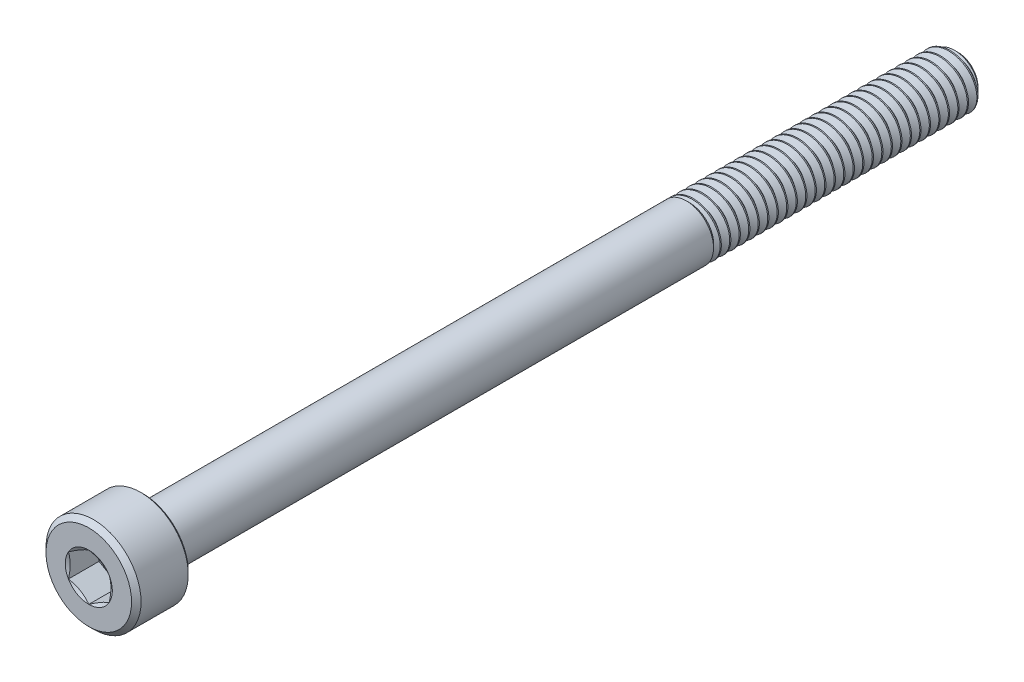
SolidWorks part; units mm, degrees
ref_plane "Front Plane" through (0, 0, 0) normal (0, 0, 1) x (1, 0, 0)
ref_plane "Top Plane" through (0, 0, 0) normal (0, 1, 0) x (1, 0, 0)
ref_plane "Right Plane" through (0, 0, 0) normal (1, 0, 0) x (0, 0, -1)
sketch "Sketch1" plane through (0, 0, 0) normal (1, 0, 0) x (0, 0, -1)
  line L0 (32, 0) -> (-32, 0) construction
  line L1 (-32, 0) -> (-32, 3.5) construction
  line L2 (-28, 2) -> (-28, 0) construction
  line L3 (31.3, 0) -> (31.3, 0.7) construction
  line L4 (12, 0) -> (12, -2) construction
  line L5 (12, 2) -> (32, 2) construction
  line L6 (32, -2) -> (32, 2) construction
  point P6 (-32, -1.5)
  point P9 (-32, 1.5)
  point P10 (12, 0)
  point P15 (-25.375, 0)
  point P16 (-23.4062, 0)
  point P17 (9.375, 0)
  point P18 (29.55, -2)
  point P22 (32, 0)
  dimension "Head Diameter" = 7
  dimension "Head Height" = 4
  dimension "Thread Size" = 4
  dimension "Length" = 60
  dimension "Thread Pitch" = 0.7
  dimension "Drive Size" = 3
  dimension "D1" = 0.7
  dimension "Min Thread Length" = 20
  dimension "D2" = 2.45
  dimension "D3" = 2.625
  dimension "D4" = 2.625
  dimension "D5" = 1.9688
sketch "Sketch2" plane through (0, 0, 0) normal (1, 0, 0) x (0, 0, -1)
  line L0 (32, 1.475) -> (31.475, 2)
  line L1 (-32, 3.5) -> (-28, 3.5)
  line L2 (-32, 3.5) -> (-32, 0)
  line L4 (-28, 3.5) -> (-28, 2)
  line L5 (-28, 2) -> (31.475, 2)
  line L8 (32, 1.475) -> (32, 0)
  line L9 (32, 0) -> (-32, 0) construction
  line L10 (32, 0) -> (-32, 0)
  dimension "D1" = 135
  dimension "D2" = 0.525
revolve "Revolve1" add sketch "Sketch2" angle 360 about L10
sketch "Sketch4" plane through (0, 0, 32) normal (0, 0, 1) x (1, 0, 0)
  line L1 (0, 1.7321) -> (-1.5, 0.866)
  line L2 (-1.5, 0.866) -> (-1.5, -0.866)
  line L3 (-1.5, -0.866) -> (0, -1.7321)
  line L4 (0, -1.7321) -> (1.5, -0.866)
  line L5 (1.5, -0.866) -> (1.5, 0.866)
  line L6 (1.5, 0.866) -> (0, 1.7321)
  circle A0 centre (0, 0) radius 1.5 construction
  circle A1 centre (0, 0) radius 3.5 construction
  circle A2 centre (0, 0) radius 3.5 construction
  circle A4 centre (0, 0) radius 3.5
  circle A5 centre (0, 0) radius 3.5 construction
  dimension "D1" = 3
extrude "Cut-Extrude1" cut sketch "Sketch4" against normal blind 2.25
sketch "Sketch5" plane through (0, 0, 32) normal (0, 0, 1) x (1, 0, 0)
  circle A0 centre (0, 0) radius 1.7321
extrude "Cut-Extrude2" cut sketch "Sketch5" against normal blind 10 draft 60
chamfer "Chamfer1" distance 0.35 angle 45 1 edges at (-3.5, 0, 32)
chamfer "Chamfer2" distance 0.175 angle 45 1 edges at (-3.5, 0, 28)
sketch "Sketch3" plane through (0, 0, -32) normal (0, 0, -1) x (-1, 0, 0)
  circle A0 centre (0, 0) radius 2 construction
  circle A1 centre (0, 0) radius 2
curve "Helix/Spiral1" pitch 0.7 height 20.7 turns 29.5714
sketch "Sketch8" plane through (0, 0, 28) normal (0, 0, -1) x (-1, 0, 0)
  circle A0 centre (0, 0) radius 2 construction
  circle A1 centre (0, 0) radius 2
sketch "Sketch7" plane through (0, 0, 0) normal (1, 0, 0) x (0, 0, -1)
  line L0 (31.9562, 2.0758) -> (32.3062, 1.4696) construction
  line L1 (32.3062, 1.4696) -> (32.6562, 2.0758) construction
  line L2 (32.6562, 2.0758) -> (31.9562, 2.0758) construction
  line L3 (32, 2) -> (32.6125, 2) construction
  line L4 (32.3062, 2.0758) -> (32.3062, 2) construction
  line L5 (32.3062, 2) -> (32.3062, 1.5453) construction
  line L6 (32.3062, 1.5453) -> (32.3062, 1.4696) construction
  line L7 (32.2625, 1.5453) -> (32.35, 1.5453)
  line L8 (31.9781, 2.0379) -> (32.6344, 2.0379)
  line L9 (32.35, 1.5453) -> (32.6344, 2.0379)
  line L10 (32.2625, 1.5453) -> (31.9781, 2.0379)
  point P0 (32.3062, 2.0379)
  dimension "D1" = 0.7
  dimension "D2" = 0.0875
sweep "Cut-Sweep1" cut profiles "Sketch7" path "Helix/Spiral1"
sketch "Sketch9" plane through (0, 0, 28) normal (0, 0, -1) x (-1, 0, 0)
  circle A0 centre (0, 0) radius 3.325 construction
  circle A1 centre (0, 0) radius 3.325
extrude "Boss-Extrude2" add sketch "Sketch9" against normal up to surface (1.75 mm away) up to face at (0, 0, 29.75)
extrude "Boss-Extrude1" add sketch "Sketch8" against normal up to surface (1.75 mm away) and the other way blind 0.7 draft 45 from vertex at 40
equation "\"D1@Sketch1\"=\"Thread Pitch@Sketch1\""
equation "\"D2@Sketch2\"=\"D1@Sketch1\"*.75"
equation "\"D4@Helix/Spiral1\"=\"Thread Pitch@Sketch1\""
equation "\"D3@Helix/Spiral1\"=\"Min Thread Length@Sketch1\"+\"Thread Pitch@Sketch1\""
equation "\"D1@Sketch4\"=\"Drive Size@Sketch1\""
equation "\"D1@Cut-Extrude1\"=\"D1@Sketch4\"*.75"
equation "\"D19\"= \"D1@Sketch4\" * .75"
equation "\"D1@Chamfer1\" = \"Head Diameter@Sketch1\" * .05"
equation "\"D1@Chamfer2\"=\"D1@Chamfer1\"/2"
equation "\"D2@Sketch7\"=\"D1@Sketch7\"/8"
equation "\"D1@Sketch7\"=\"D4@Helix/Spiral1\""
equation "\"D2@Boss-Extrude1\"=\"Thread Pitch@Sketch1\"*1"
equation "\"D2@Sketch1\"=\"Thread Pitch@Sketch1\"*3.5"
equation "\"D3@Sketch1\" = \"Head Diameter@Sketch1\" * .375"
equation "\"D4@Sketch1\"=\"D3@Sketch1\""
equation "\"D5@Sketch1\"=\"D4@Sketch1\"*.75"
